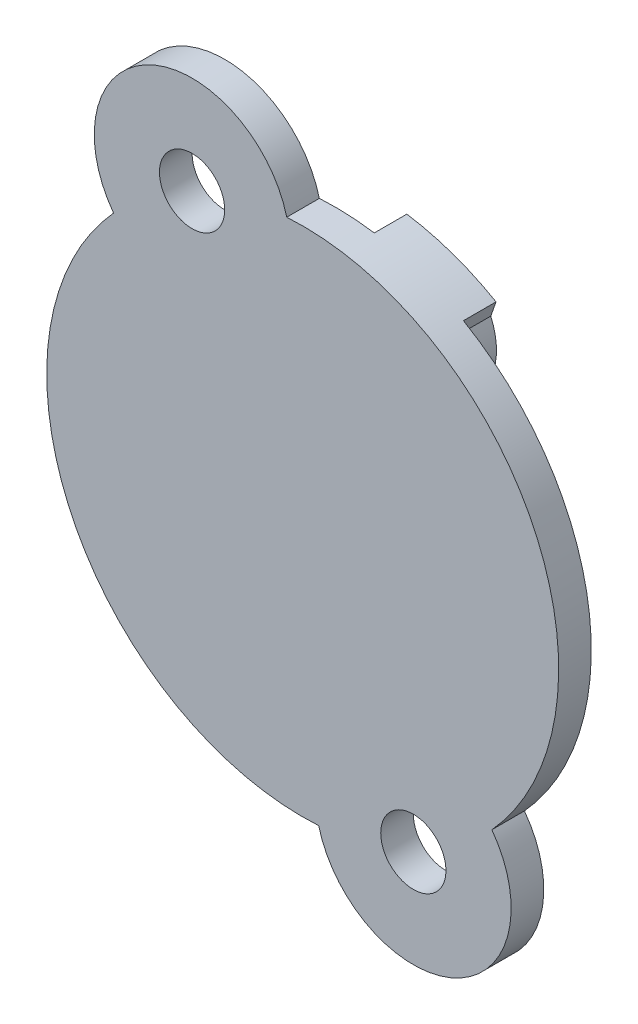
SolidWorks part; units mm, degrees
ref_plane "Front Plane" through (0, 0, 0) normal (0, 0, 1) x (1, 0, 0)
ref_plane "Top Plane" through (0, 0, 0) normal (0, 1, 0) x (1, 0, 0)
ref_plane "Right Plane" through (0, 0, 0) normal (1, 0, 0) x (0, 0, -1)
sketch "Sketch1" plane through (0, 0, 0) normal (0, 0, 1) x (1, 0, 0)
  circle A0 centre (0, 0) radius 7.85
  dimension "D1" = 15.7
extrude "Boss-Extrude1" add sketch "Sketch1" along normal blind 1
sketch "Sketch2" plane through (0, 0, 0) normal (0, 0, -1) x (-1, 0, 0)
  circle A0 centre (3.3929, 7.0789) radius 1 construction
  arc A1 (5.8006, 5.2892) -> (0.4896, 7.8347) centre (3.3929, 7.0789) ccw construction
  circle A2 centre (-3.3929, -7.0789) radius 1 construction
  arc A3 (-5.8006, -5.2892) -> (-0.4896, -7.8347) centre (-3.3929, -7.0789) ccw construction
  circle A4 centre (3.3929, 7.0789) radius 1
  arc A5 (5.8006, 5.2892) -> (0.4896, 7.8347) centre (3.3929, 7.0789) ccw
  circle A6 centre (-3.3929, -7.0789) radius 1
  arc A7 (-5.8006, -5.2892) -> (-0.4896, -7.8347) centre (-3.3929, -7.0789) ccw
  circle M1 centre (0, 0) radius 7.85
sketch "Sketch3" plane through (0, 0, 0) normal (0, 0, -1) x (-1, 0, 0)
  line L0 (-3.7675, 6.336) -> (-3.9293, 6.7958) construction
  line L1 (-3.7675, 6.336) -> (-3.9293, 6.7958)
  line L2 (-1.032, 7.2989) -> (-1.1939, 7.7587) construction
  line L3 (-1.032, 7.2989) -> (-1.1939, 7.7587)
  line L7 (1.1939, -7.7587) -> (1.032, -7.2989) construction
  line L8 (3.9293, -6.7958) -> (3.7675, -6.336) construction
  line L9 (1.1939, -7.7587) -> (1.032, -7.2989)
  line L10 (3.9293, -6.7958) -> (3.7675, -6.336)
  circle A0 centre (0, 0) radius 6
  arc A1 (-5.8006, -5.2892) -> (-0.4896, -7.8347) centre (-3.3929, -7.0789) ccw construction
  arc A2 (-5.8006, -5.2892) -> (-0.4896, -7.8347) centre (-3.3929, -7.0789) ccw
  arc A3 (5.8006, 5.2892) -> (0.4896, 7.8347) centre (3.3929, 7.0789) ccw construction
  arc A4 (5.8006, 5.2892) -> (0.4896, 7.8347) centre (3.3929, 7.0789) ccw
  circle A5 centre (3.3929, 7.0789) radius 1 construction
  circle A6 centre (3.3929, 7.0789) radius 1
  circle A7 centre (-3.3929, -7.0789) radius 1 construction
  circle A8 centre (-3.3929, -7.0789) radius 1
  circle A9 centre (0, 0) radius 7.85 construction
  circle A10 centre (0, 0) radius 7.85
  circle A11 centre (0, 0) radius 4.5
  arc A12 (-3.7675, 6.336) -> (-3.7573, 4.6779) centre (-1.9424, 5.5181) ccw construction
  arc A13 (-3.7675, 6.336) -> (-3.7573, 4.6779) centre (-1.9424, 5.5181) ccw
  arc A14 (-0.0013, 6) -> (-1.032, 7.2989) centre (-1.9424, 5.5181) ccw construction
  arc A15 (-0.0013, 6) -> (-1.032, 7.2989) centre (-1.9424, 5.5181) ccw
  arc A16 (3.7675, -6.336) -> (3.7573, -4.6779) centre (1.9424, -5.5181) ccw construction
  arc A17 (0.0013, -6) -> (1.032, -7.2989) centre (1.9424, -5.5181) ccw construction
  arc A18 (3.7675, -6.336) -> (3.7573, -4.6779) centre (1.9424, -5.5181) ccw
  arc A19 (0.0013, -6) -> (1.032, -7.2989) centre (1.9424, -5.5181) ccw
  circle M12 centre (0, 0) radius 7.85
  dimension "D1" = 9
extrude "Boss-Extrude2" add sketch "Sketch3" along normal blind 1 contours A0 A11 | A0 A19 L9 L10 A18 M12 | A0 A15 L3 L1 A13 M12 region at (2.2496, 6.3908, 0) region at (1.9358, 5.4995, 0) region at (-2.2496, -6.3908, 0)
extrude "Boss-Extrude3" add sketch "Sketch2" against normal blind 1 contours A7 A6 M1 | A5 A4 M1 region at (-3.9345, 8.2089, 0) region at (3.9345, -8.2089, 0)
extrude "Cut-Extrude1" cut sketch "Sketch2<3>" against normal blind 2 contours A4
sketch "Sketch2<3>" plane through (0, 0, 0) normal (0, 0, -1) x (-1, 0, 0) same geometry as "Sketch2"
extrude "Cut-Extrude2" cut sketch "Sketch2<4>" against normal blind 3 contours A6
sketch "Sketch2<4>" plane through (0, 0, 0) normal (0, 0, -1) x (-1, 0, 0) same geometry as "Sketch2"
